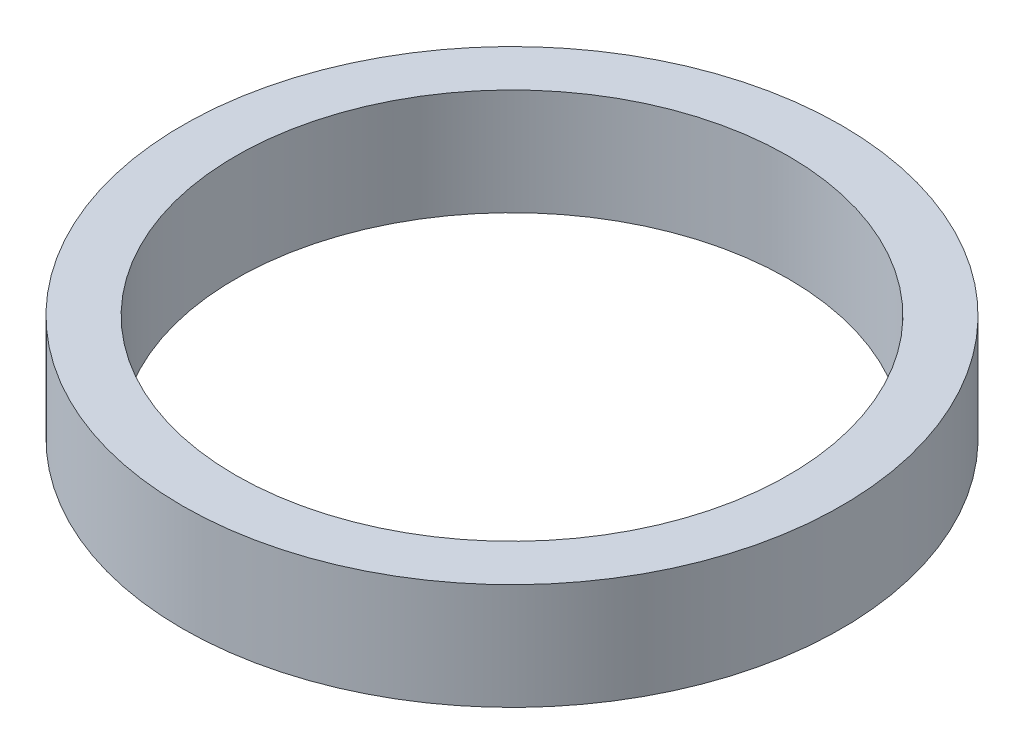
SolidWorks part; units mm, degrees
ref_plane "Front Plane" through (0, 0, 0) normal (0, 0, 1) x (1, 0, 0)
ref_plane "Top Plane" through (0, 0, 0) normal (0, 1, 0) x (1, 0, 0)
ref_plane "Right Plane" through (0, 0, 0) normal (1, 0, 0) x (0, 0, -1)
sketch "Sketch1" plane through (0, 0, 0) normal (0, 1, 0) x (1, 0, 0)
  circle A0 centre (0, 0) radius 26
  circle A1 centre (0, 0) radius 31
  dimension "D1" = 52
  dimension "D2" = 62
extrude "Boss-Extrude1" add sketch "Sketch1" along normal blind 10
